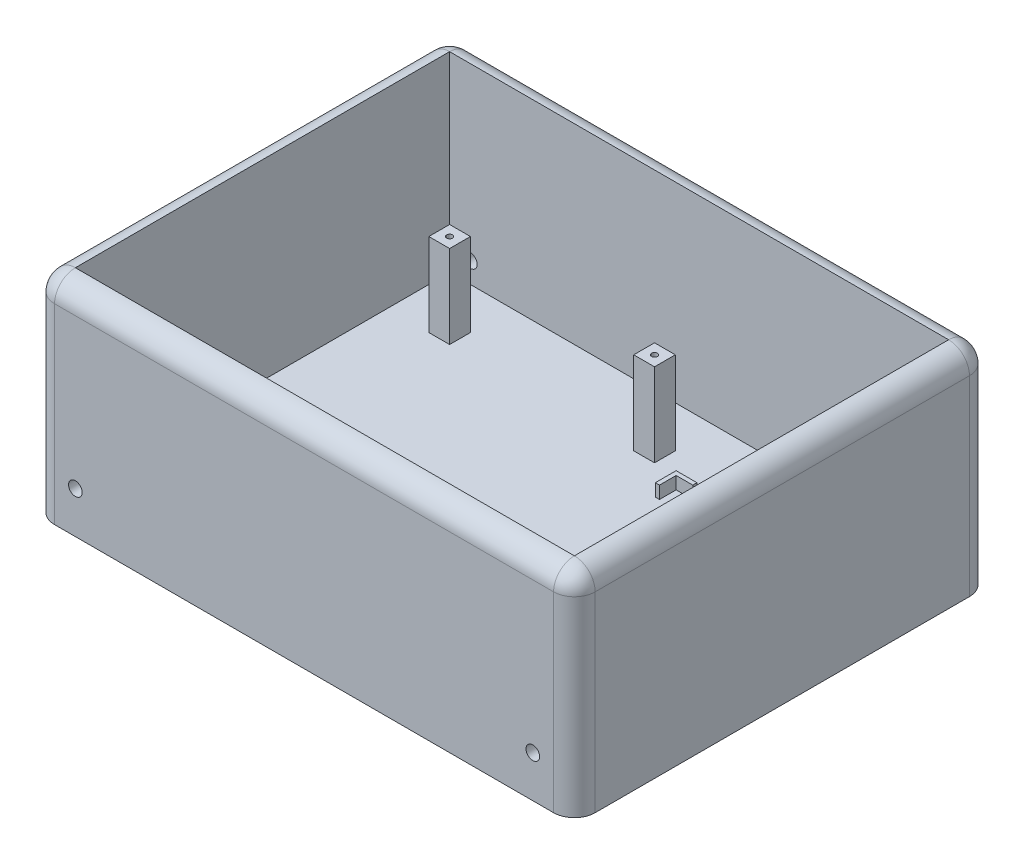
SolidWorks part; units mm, degrees
ref_plane "Front Plane" through (0, 0, 0) normal (0, 0, 1) x (1, 0, 0)
ref_plane "Top Plane" through (0, 0, 0) normal (0, 1, 0) x (1, 0, 0)
ref_plane "Right Plane" through (0, 0, 0) normal (1, 0, 0) x (0, 0, -1)
sketch "Sketch1" plane through (0, 0, 0) normal (0, 1, 0) x (1, 0, 0)
  line L1 (-65, 50) -> (65, 50)
  line L2 (-65, 50) -> (-65, -50)
  line L3 (-65, -50) -> (65, -50)
  line L4 (65, 50) -> (65, -50)
  line L5 (-65, 50) -> (65, -50) construction
  line L6 (-65, -50) -> (65, 50) construction
  point P0 (0, 0)
  dimension "D1" = 130
  dimension "D2" = 100
extrude "Boss-Extrude1" add sketch "Sketch1" along normal blind 51
sketch "Sketch2" plane through (0, 51, 0) normal (0, 1, 0) x (1, 0, 0)
  line L0 (-65, 50) -> (-65, -50) construction
  line L1 (-60, -45) -> (60, -45)
  line L2 (-60, -45) -> (-60, 45)
  line L3 (-60, 45) -> (60, 45)
  line L4 (60, -45) -> (60, 45)
  line L5 (-60, -45) -> (60, 45) construction
  line L6 (-60, 45) -> (60, -45) construction
  line L7 (65, 50) -> (-65, 50) construction
  point P0 (0, 0)
  dimension "D1" = 5
  dimension "D2" = 5
extrude "Cut-Extrude1" cut sketch "Sketch2" against normal blind 46
fillet "Fillet2" radius 5 4 edges at (0, 51, -50) (65, 51, 0) (0, 51, 50) (-65, 51, 0)
fillet "Fillet4" radius 5 8 edges at (65, 23, -50) (-65, 23, -50) (65, 23, 50) (-65, 23, 50) (63.5355, 49.5355, -48.5355) (-63.5355, 49.5355, -48.5355) (63.5355, 49.5355, 48.5355) (-63.5355, 49.5355, 48.5355)
sketch "Sketch6" plane through (0, 5, 0) normal (0, 1, 0) x (1, 0, 0)
  line L0 (60, 45) -> (-60, 45) construction
  line L1 (-50, 35) -> (-45, 35)
  line L2 (-50, 35) -> (-50, 30)
  line L3 (-50, 30) -> (-45, 30)
  line L4 (-45, 35) -> (-45, 30)
  line L5 (-50, 35) -> (-45, 30) construction
  line L6 (-50, 30) -> (-45, 35) construction
  line L7 (-50, -29.03) -> (-45, -29.03)
  line L8 (-50, -29.03) -> (-50, -34.03)
  line L9 (-50, -34.03) -> (-45, -34.03)
  line L10 (-45, -29.03) -> (-45, -34.03)
  line L11 (-50, -29.03) -> (-45, -34.03) construction
  line L12 (-50, -34.03) -> (-45, -29.03) construction
  line L13 (-0.73, 35) -> (4.27, 35)
  line L14 (-0.73, 35) -> (-0.73, 30)
  line L15 (-0.73, 30) -> (4.27, 30)
  line L16 (4.27, 35) -> (4.27, 30)
  line L17 (-0.73, 35) -> (4.27, 30) construction
  line L18 (-0.73, 30) -> (4.27, 35) construction
  line L24 (-0.73, -29.03) -> (4.27, -29.03)
  line L25 (-60, 45) -> (-60, -45) construction
  line L26 (-0.73, -29.03) -> (-0.73, -34.03)
  line L27 (-0.73, -34.03) -> (4.27, -34.03)
  line L28 (4.27, -29.03) -> (4.27, -34.03)
  line L29 (-0.73, -29.03) -> (4.27, -34.03) construction
  line L30 (-0.73, -34.03) -> (4.27, -29.03) construction
  point P0 (-47.5, 32.5)
  point P5 (-47.5, -31.53)
  point P10 (1.77, 32.5)
  point P15 (1.77, -31.53)
  dimension "D1" = 5
  dimension "D2" = 5
  dimension "D3" = 5
  dimension "D4" = 5
  dimension "D5" = 44.27
  dimension "D6" = 59.03
  dimension "D7" = 10
  dimension "D8" = 10
extrude "Boss-Extrude2" add sketch "Sketch6" along normal blind 20
sketch "Sketch9" plane through (0, 5, 0) normal (0, 1, 0) x (1, 0, 0)
  line L0 (11.5, -14.03) -> (11.5, -19.03)
  line L1 (11.5, -19.03) -> (16.5, -19.03)
  line L2 (16.5, -19.03) -> (16.5, -18.03)
  line L3 (16.5, -18.03) -> (12.5, -18.03)
  line L4 (12.5, -18.03) -> (12.5, -14.03)
  line L5 (12.5, -14.03) -> (11.5, -14.03)
  line L6 (11.5, 27.97) -> (16.5, 27.97)
  line L7 (16.5, 27.97) -> (16.5, 26.97)
  line L8 (16.5, 26.97) -> (12.5, 26.97)
  line L9 (12.5, 26.97) -> (12.5, 22.97)
  line L10 (12.5, 22.97) -> (11.5, 22.97)
  line L11 (11.5, 22.97) -> (11.5, 27.97)
  line L12 (40, 27.97) -> (40, 22.97)
  line L13 (40, 22.97) -> (39, 22.97)
  line L14 (39, 22.97) -> (39, 26.97)
  line L15 (39, 26.97) -> (35, 26.97)
  line L16 (35, 26.97) -> (35, 27.97)
  line L17 (35, 27.97) -> (40, 27.97)
  line L18 (40, -19.03) -> (35, -19.03)
  line L19 (35, -19.03) -> (35, -18.03)
  line L20 (35, -18.03) -> (39, -18.03)
  line L21 (39, -18.03) -> (39, -14.03)
  line L22 (39, -14.03) -> (40, -14.03)
  line L23 (40, -14.03) -> (40, -19.03)
  line L24 (60, -45) -> (60, 45) construction
  line L25 (4.27, -29.03) -> (-0.73, -29.03) construction
  dimension "D1" = 5
  dimension "D2" = 1
  dimension "D3" = 5
  dimension "D4" = 1
  dimension "D5" = 1
  dimension "D6" = 5
  dimension "D7" = 1
  dimension "D8" = 5
  dimension "D9" = 1
  dimension "D10" = 5
  dimension "D11" = 5
  dimension "D12" = 1
  dimension "D13" = 5
  dimension "D14" = 5
  dimension "D15" = 1
  dimension "D16" = 1
  dimension "D17" = 45
  dimension "D18" = 26.5
  dimension "D19" = 20
  dimension "D20" = 10
extrude "Boss-Extrude3" add sketch "Sketch9" along normal blind 3
hole_wizard "#00 Clearance Hole1" positions "Sketch13" profile "Sketch14" hole size "#00" standard "ANSI Inch"
sketch "Sketch13" plane through (58.9654, 25, -19.1453) normal (0, 1, 0) x (1, 0, 0)
  point P0 (-106.4654, -50.6753)
  point P1 (-57.1954, -50.6753)
  point P2 (-57.1954, 13.3547)
  point P3 (-106.4654, 13.3547)
  point P12 (-55.8951, 15.8547)
sketch "Sketch14" plane through (-47.5, 25, 31.53) normal (1, 0, 0) x (0, 0, 1)
  line L0 (0, 0) -> (0, 20)
  line L1 (0, 20) -> (0.6985, 20)
  line L2 (0.6985, 20) -> (0.6985, 0)
  line L3 (0.6985, 0) -> (0, 0)
  line L4 (0, -6.35) -> (0, 107.95) construction
  dimension "Thru Hole Dia." = 1.397
  dimension "Thru Hole Depth" = 20
hole_wizard "#4 Clearance Hole1" positions "Sketch17" profile "Sketch18" hole size "#4" standard "ANSI Inch" end condition through all
sketch "Sketch17" plane through (58.9654, 7.3812, 50) normal (0, 0, 1) x (1, 0, 0)
  point P0 (-3.9654, 2.6188)
  point P1 (-113.9654, 2.6188)
sketch "Sketch18" plane through (55, 10, 50) normal (1, 0, 0) x (0, -1, 0)
  line L0 (0, 0) -> (0, 100)
  line L1 (0, 100) -> (1.6319, 100)
  line L2 (1.6319, 100) -> (1.6319, 0)
  line L3 (1.6319, 0) -> (0, 0)
  line L4 (0, -6.35) -> (0, 107.95) construction
  dimension "Thru Hole Dia." = 3.2639
  dimension "Thru Hole Depth" = 100
